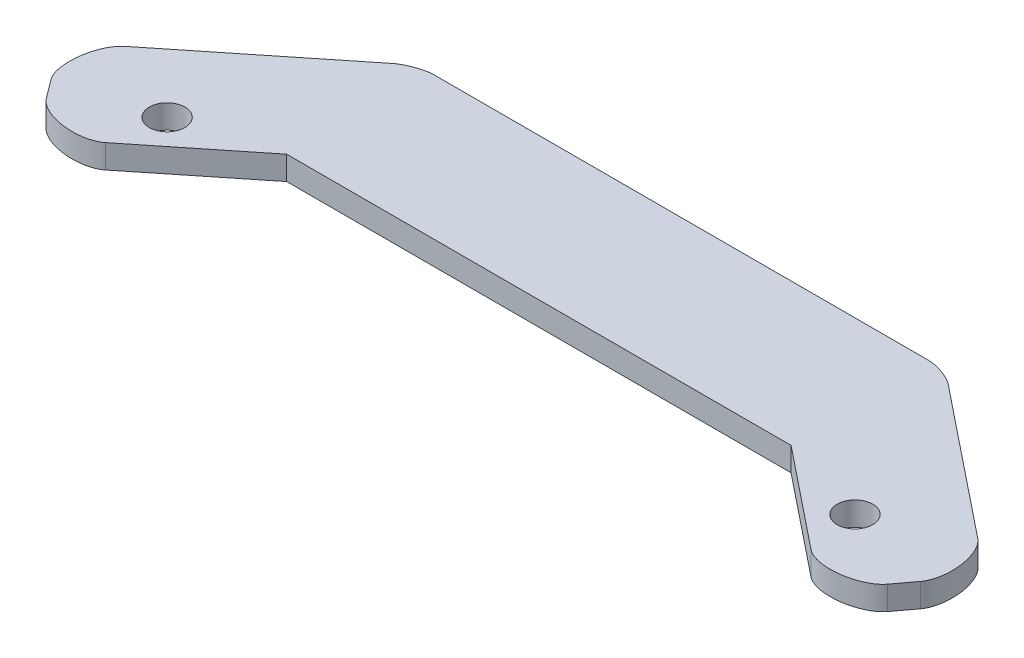
SolidWorks part; units mm, degrees
ref_plane "Front Plane" through (0, 0, 0) normal (0, 0, 1) x (1, 0, 0)
ref_plane "Top Plane" through (0, 0, 0) normal (0, 1, 0) x (1, 0, 0)
ref_plane "Right Plane" through (0, 0, 0) normal (1, 0, 0) x (0, 0, -1)
sketch "Sketch1" plane through (0, 0, 0) normal (0, 1, 0) x (1, 0, 0)
  line L0 (-13.635, -43.1454) -> (0.2556, -60.4948) construction
  line L5 (-13.635, -43.1454) -> (-22.9293, -50.5868) construction
  line L6 (-22.9293, -50.5868) -> (-9.0387, -67.9362) construction
  line L7 (-22.1678, 36.7724) -> (28.6322, 36.7724) construction
  line L8 (-22.1678, 36.7724) -> (-22.1678, -191.8276) construction
  line L9 (-22.1678, -191.8276) -> (28.6322, -191.8276) construction
  line L10 (28.6322, 36.7724) -> (28.6322, -191.8276) construction
  line L11 (0.2556, -60.4948) -> (-9.0387, -67.9362) construction
  line L12 (-13.635, -24.0954) -> (0.2556, -41.4448) construction
  line L13 (-13.635, -24.0954) -> (-22.9293, -31.5368) construction
  line L14 (-22.9293, -31.5368) -> (-9.0387, -48.8862) construction
  line L15 (-8.1122, -59.5683) -> (-27.1622, -59.5683) construction
  line L16 (-8.1122, -59.5683) -> (-8.1122, -40.5183) construction
  line L17 (0.2556, -41.4448) -> (-9.0387, -48.8862) construction
  line L18 (-8.1122, -40.5183) -> (-27.1622, -40.5183) construction
  line L19 (-8.1122, -40.5183) -> (-8.1122, -21.4683) construction
  line L20 (-13.635, -100.2954) -> (0.2556, -117.6448) construction
  line L21 (-13.635, -100.2954) -> (-22.9293, -107.7368) construction
  line L22 (-22.9293, -107.7368) -> (-9.0387, -125.0862) construction
  line L23 (0.2556, -117.6448) -> (-9.0387, -125.0862) construction
  line L24 (-13.635, -81.2454) -> (0.2556, -98.5948) construction
  line L25 (-13.635, -81.2454) -> (-22.9293, -88.6868) construction
  line L26 (-22.9293, -88.6868) -> (-9.0387, -106.0362) construction
  line L27 (-8.1122, -116.7183) -> (-27.1622, -116.7183) construction
  line L28 (-8.1122, -116.7183) -> (-8.1122, -97.6683) construction
  line L29 (0.2556, -98.5948) -> (-9.0387, -106.0362) construction
  line L30 (-8.1122, -97.6683) -> (-27.1622, -97.6683) construction
  line L31 (-8.1122, -97.6683) -> (-8.1122, -78.6183) construction
  line L32 (-13.635, -5.0454) -> (0.2556, -22.3948) construction
  line L33 (-13.635, -5.0454) -> (-22.9293, -12.4868) construction
  line L34 (-13.635, 14.0046) -> (0.2556, -3.3448) construction
  line L35 (-13.635, 14.0046) -> (-22.9293, 6.5632) construction
  line L36 (-22.9293, 6.5632) -> (-9.0387, -10.7862) construction
  line L37 (0.2556, -3.3448) -> (-9.0387, -10.7862) construction
  line L38 (-22.9293, -12.4868) -> (-9.0387, -29.8362) construction
  line L39 (0.2556, -22.3948) -> (-9.0387, -29.8362) construction
  line L40 (-13.635, 33.0546) -> (0.2556, 15.7052) construction
  line L41 (-13.635, 33.0546) -> (-22.9293, 25.6132) construction
  line L42 (-22.9293, 25.6132) -> (-9.0387, 8.2638) construction
  line L43 (0.2556, 15.7052) -> (-9.0387, 8.2638) construction
  line L44 (-8.1122, -21.4683) -> (-27.1622, -21.4683) construction
  line L45 (-8.1122, -21.4683) -> (-8.1122, -2.4183) construction
  line L46 (-13.635, -62.1954) -> (0.2556, -79.5448) construction
  line L47 (-13.635, -62.1954) -> (-22.9293, -69.6368) construction
  line L48 (-22.9293, -69.6368) -> (-9.0387, -86.9862) construction
  line L49 (0.2556, -79.5448) -> (-9.0387, -86.9862) construction
  line L50 (-8.1122, -78.6183) -> (-27.1622, -78.6183) construction
  line L51 (-8.1122, -78.6183) -> (-8.1122, -59.5683) construction
  line L52 (-8.1122, -2.4183) -> (-27.1622, -2.4183) construction
  line L53 (-8.1122, -2.4183) -> (-8.1122, 16.6317) construction
  line L54 (-8.1122, 16.6317) -> (-27.1622, 16.6317) construction
  line L55 (-8.1122, 16.6317) -> (-8.1122, 35.6817) construction
  line L56 (-22.9293, 25.6132) -> (-25.9059, 29.3309) construction
  line L57 (-25.9059, 29.3309) -> (-16.6116, 36.7724) construction
  line L58 (-16.6116, 36.7724) -> (-13.635, 33.0546) construction
  line L59 (-24.4176, 27.4721) -> (-15.1233, 34.9135) construction
  line L60 (-25.9059, 28.8165) -> (-25.9059, 40.1202) construction
  line L61 (-9.0387, 8.2638) -> (-6.0621, 4.5461) construction
  line L62 (-8.1122, 36.5878) -> (-8.1122, -24.5097) construction
  line L63 (-6.0621, 4.5461) -> (3.2322, 11.9875) construction
  line L64 (0.2556, 15.7052) -> (3.2322, 11.9875) construction
  line L65 (1.7439, 13.8464) -> (-7.5504, 6.405) construction
  line L66 (-19.7704, 30.6783) -> (-19.7704, 38.979) construction
  line L67 (-2.9032, 9.6112) -> (-2.9032, 17.9119) construction
  line L68 (3.2322, 11.4731) -> (3.2322, 48.1829) construction
  line L69 (4.7205, 13.8464) -> (14.0148, 6.405) construction
  line L70 (6.2088, 15.7052) -> (3.2322, 11.9875) construction
  line L71 (12.5265, 4.5461) -> (3.2322, 11.9875) construction
  line L72 (15.5031, 8.2638) -> (12.5265, 4.5461) construction
  line L73 (30.882, 27.4721) -> (21.5877, 34.9135) construction
  line L74 (23.0759, 36.7724) -> (20.0994, 33.0546) construction
  line L75 (32.3703, 29.3309) -> (23.0759, 36.7724) construction
  line L76 (29.3937, 25.6132) -> (32.3703, 29.3309) construction
  line L77 (14.5766, 16.6317) -> (14.5766, 35.6817) construction
  line L78 (14.5766, 16.6317) -> (33.6266, 16.6317) construction
  line L79 (14.5766, -2.4183) -> (14.5766, 16.6317) construction
  line L80 (14.5766, -2.4183) -> (33.6266, -2.4183) construction
  line L81 (14.5766, -78.6183) -> (14.5766, -59.5683) construction
  line L82 (14.5766, -78.6183) -> (33.6266, -78.6183) construction
  line L83 (6.2088, -79.5448) -> (15.5031, -86.9862) construction
  line L84 (29.3937, -69.6368) -> (15.5031, -86.9862) construction
  line L85 (20.0994, -62.1954) -> (29.3937, -69.6368) construction
  line L86 (20.0994, -62.1954) -> (6.2088, -79.5448) construction
  line L87 (14.5766, -21.4683) -> (14.5766, -2.4183) construction
  line L88 (14.5766, -21.4683) -> (33.6266, -21.4683) construction
  line L89 (6.2088, 15.7052) -> (15.5031, 8.2638) construction
  line L90 (29.3937, 25.6132) -> (15.5031, 8.2638) construction
  line L91 (20.0994, 33.0546) -> (29.3937, 25.6132) construction
  line L92 (20.0994, 33.0546) -> (6.2088, 15.7052) construction
  line L93 (6.2088, -22.3948) -> (15.5031, -29.8362) construction
  line L94 (29.3937, -12.4868) -> (15.5031, -29.8362) construction
  line L95 (6.2088, -3.3448) -> (15.5031, -10.7862) construction
  line L96 (29.3937, 6.5632) -> (15.5031, -10.7862) construction
  line L97 (20.0994, 14.0046) -> (29.3937, 6.5632) construction
  line L98 (20.0994, 14.0046) -> (6.2088, -3.3448) construction
  line L99 (20.0994, -5.0454) -> (29.3937, -12.4868) construction
  line L100 (20.0994, -5.0454) -> (6.2088, -22.3948) construction
  line L101 (14.5766, -97.6683) -> (14.5766, -78.6183) construction
  line L102 (14.5766, -97.6683) -> (33.6266, -97.6683) construction
  line L103 (6.2088, -98.5948) -> (15.5031, -106.0362) construction
  line L104 (14.5766, -116.7183) -> (14.5766, -97.6683) construction
  line L105 (14.5766, -116.7183) -> (33.6266, -116.7183) construction
  line L106 (29.3937, -88.6868) -> (15.5031, -106.0362) construction
  line L107 (20.0994, -81.2454) -> (29.3937, -88.6868) construction
  line L108 (20.0994, -81.2454) -> (6.2088, -98.5948) construction
  line L109 (6.2088, -117.6448) -> (15.5031, -125.0862) construction
  line L110 (29.3937, -107.7368) -> (15.5031, -125.0862) construction
  line L111 (20.0994, -100.2954) -> (29.3937, -107.7368) construction
  line L112 (20.0994, -100.2954) -> (6.2088, -117.6448) construction
  line L113 (14.5766, -40.5183) -> (14.5766, -21.4683) construction
  line L114 (14.5766, -40.5183) -> (33.6266, -40.5183) construction
  line L115 (6.2088, -41.4448) -> (15.5031, -48.8862) construction
  line L116 (14.5766, -59.5683) -> (14.5766, -40.5183) construction
  line L117 (14.5766, -59.5683) -> (33.6266, -59.5683) construction
  line L118 (29.3937, -31.5368) -> (15.5031, -48.8862) construction
  line L119 (20.0994, -24.0954) -> (29.3937, -31.5368) construction
  line L120 (20.0994, -24.0954) -> (6.2088, -41.4448) construction
  line L121 (6.2088, -60.4948) -> (15.5031, -67.9362) construction
  line L122 (29.3937, -50.5868) -> (15.5031, -67.9362) construction
  line L123 (20.0994, -43.1454) -> (29.3937, -50.5868) construction
  line L124 (20.0994, -43.1454) -> (6.2088, -60.4948) construction
  line L125 (23.0759, 36.7724) -> (-16.6116, 36.7724) construction
  circle A2 centre (-8.1122, -59.5683) radius 5.9531 construction
  circle A3 centre (-8.1122, -59.5683) radius 19.05 construction
  circle A4 centre (-8.1122, -40.5183) radius 5.9531 construction
  circle A5 centre (-8.1122, -40.5183) radius 19.05 construction
  circle A6 centre (-8.1122, -116.7183) radius 5.9531 construction
  circle A7 centre (-8.1122, -116.7183) radius 19.05 construction
  circle A8 centre (-8.1122, -97.6683) radius 5.9531 construction
  circle A9 centre (-8.1122, -97.6683) radius 19.05 construction
  circle A10 centre (-8.1122, -2.4183) radius 5.9531 construction
  circle A11 centre (-8.1122, -2.4183) radius 19.05 construction
  circle A12 centre (-8.1122, 16.6317) radius 5.9531 construction
  circle A13 centre (-8.1122, 16.6317) radius 19.05 construction
  circle A14 centre (-8.1122, -21.4683) radius 5.9531 construction
  circle A15 centre (-8.1122, -21.4683) radius 19.05 construction
  circle A16 centre (-8.1122, -78.6183) radius 5.9531 construction
  circle A17 centre (-8.1122, -78.6183) radius 19.05 construction
  circle A18 centre (-19.7704, 31.1928) radius 1.1906
  circle A19 centre (-2.9032, 10.1257) radius 1.1906
  circle A20 centre (14.5766, -78.6183) radius 19.05 construction
  circle A21 centre (14.5766, -78.6183) radius 5.9531 construction
  circle A22 centre (14.5766, -21.4683) radius 19.05 construction
  circle A23 centre (14.5766, -21.4683) radius 5.9531 construction
  circle A24 centre (14.5766, 16.6317) radius 19.05 construction
  circle A25 centre (14.5766, 16.6317) radius 5.9531 construction
  circle A26 centre (14.5766, -2.4183) radius 19.05 construction
  circle A27 centre (14.5766, -2.4183) radius 5.9531 construction
  circle A28 centre (14.5766, -97.6683) radius 19.05 construction
  circle A29 centre (14.5766, -97.6683) radius 5.9531 construction
  circle A30 centre (14.5766, -116.7183) radius 19.05 construction
  circle A31 centre (14.5766, -116.7183) radius 5.9531 construction
  circle A32 centre (14.5766, -40.5183) radius 19.05 construction
  circle A33 centre (14.5766, -40.5183) radius 5.9531 construction
  circle A34 centre (14.5766, -59.5683) radius 19.05 construction
  circle A35 centre (14.5766, -59.5683) radius 5.9531 construction
  circle A36 centre (9.3676, 10.1257) radius 1.1906
  circle A37 centre (26.2348, 31.1928) radius 1.1906
  point P81 (-15.1233, 34.9135)
  point P97 (3.2322, 36.7724)
  dimension "D3" = 2.3813
  dimension "D23" = 38.1
  dimension "D1" = 4.7625
  dimension "D4" = 50.8
  dimension "D5" = 228.6
  dimension "D21" = 22.225
  dimension "D22" = 11.9062
sketch "Sketch2" plane through (0, 0, 0) normal (0, 1, 0) x (1, 0, 0)
  line L0 (-16.6116, 36.7724) -> (-13.635, 33.0546)
  line L1 (-13.635, 33.0546) -> (-22.9293, 25.6132)
  line L2 (-22.9293, 25.6132) -> (-13.635, 14.0046)
  line L3 (-18.2822, 10.2839) -> (-19.7704, 12.1428)
  line L4 (-13.635, 14.0046) -> (-22.9293, 6.5632) construction
  line L5 (-19.7704, -199969.3217) -> (-19.7704, 200038.979) construction
  line L6 (3.2322, 37.6418) -> (3.2322, 34.7632) construction
  line L7 (-9.0387, -10.7862) -> (0.2556, -22.3948)
  line L8 (3.2322, -199988.5269) -> (3.2322, 200048.1829) construction
  line L9 (-13.635, 14.0046) -> (-22.9293, 6.5632)
  line L10 (-22.9293, 6.5632) -> (-13.635, -5.0454)
  line L11 (-13.635, -5.0454) -> (-22.9293, -12.4868)
  line L12 (-22.9293, -12.4868) -> (-13.635, -24.0954)
  line L13 (-13.635, -24.0954) -> (-22.9293, -31.5368)
  line L14 (-22.9293, -31.5368) -> (-13.635, -43.1454)
  line L15 (-13.635, -43.1454) -> (-22.9293, -50.5868)
  line L16 (-22.9293, -50.5868) -> (-13.635, -62.1954)
  line L17 (-13.635, -62.1954) -> (-22.9293, -69.6368)
  line L18 (-22.9293, -69.6368) -> (-13.635, -81.2454)
  line L19 (-13.635, -81.2454) -> (-22.9293, -88.6868)
  line L20 (-22.9293, -88.6868) -> (-13.635, -100.2954)
  line L21 (-13.635, -100.2954) -> (-22.9293, -107.7368)
  line L22 (-22.9293, -107.7368) -> (-13.635, -119.3454)
  line L23 (0.2556, 15.7052) -> (-9.0387, 8.2638)
  line L24 (-9.0387, 8.2638) -> (0.2556, -3.3448)
  line L25 (0.2556, -3.3448) -> (-9.0387, -10.7862)
  line L26 (-9.0387, -29.8362) -> (0.2556, -41.4448)
  line L27 (0.2556, -22.3948) -> (-9.0387, -29.8362)
  line L28 (-9.0387, -48.8862) -> (0.2556, -60.4948)
  line L29 (0.2556, -41.4448) -> (-9.0387, -48.8862)
  line L30 (-9.0387, -67.9362) -> (0.2556, -79.5448)
  line L31 (0.2556, -60.4948) -> (-9.0387, -67.9362)
  line L32 (-9.0387, -86.9862) -> (0.2556, -98.5948)
  line L33 (0.2556, -79.5448) -> (-9.0387, -86.9862)
  line L34 (-9.0387, -106.0362) -> (0.2556, -117.6448)
  line L35 (0.2556, -98.5948) -> (-9.0387, -106.0362)
  line L37 (0.2556, -117.6448) -> (-9.0387, -125.0862)
  line L38 (6.2088, -117.6448) -> (15.5031, -125.0862)
  line L39 (-9.0387, -125.0862) -> (0.2556, -136.6948)
  line L41 (-22.9293, 25.6132) -> (-27.6918, 25.6132) construction
  line L42 (-16.6116, 36.7724) -> (-27.6918, 36.7724)
  line L43 (-27.6918, 36.7724) -> (-27.6918, -124.1079)
  line L44 (-13.635, -119.3454) -> (-13.635, -124.1079)
  line L45 (-13.635, -124.1079) -> (-27.6918, -124.1079)
  line L47 (6.2088, -98.5948) -> (15.5031, -106.0362)
  line L48 (15.5031, -106.0362) -> (6.2088, -117.6448)
  line L49 (6.2088, -79.5448) -> (15.5031, -86.9862)
  line L50 (15.5031, -86.9862) -> (6.2088, -98.5948)
  line L51 (6.2088, -60.4948) -> (15.5031, -67.9362)
  line L52 (15.5031, -67.9362) -> (6.2088, -79.5448)
  line L53 (6.2088, -41.4448) -> (15.5031, -48.8862)
  line L54 (15.5031, -48.8862) -> (6.2088, -60.4948)
  line L55 (6.2088, -22.3948) -> (15.5031, -29.8362)
  line L56 (15.5031, -29.8362) -> (6.2088, -41.4448)
  line L57 (6.2088, -3.3448) -> (15.5031, -10.7862)
  line L58 (15.5031, 8.2638) -> (6.2088, -3.3448)
  line L59 (6.2088, 15.7052) -> (15.5031, 8.2638)
  line L60 (15.5031, -10.7862) -> (6.2088, -22.3948)
  line L61 (0.2556, 15.7052) -> (6.2088, 15.7052)
  line L62 (29.3937, 25.6132) -> (34.1562, 25.6132) construction
  line L63 (20.0994, -124.1079) -> (34.1562, -124.1079)
  line L64 (20.0994, -119.3454) -> (20.0994, -124.1079)
  line L65 (34.1562, 36.7724) -> (34.1562, -124.1079)
  line L66 (23.0759, 36.7724) -> (34.1562, 36.7724)
  line L67 (29.3937, -107.7368) -> (20.0994, -119.3454)
  line L68 (20.0994, -100.2954) -> (29.3937, -107.7368)
  line L69 (29.3937, -88.6868) -> (20.0994, -100.2954)
  line L70 (20.0994, -81.2454) -> (29.3937, -88.6868)
  line L71 (29.3937, -69.6368) -> (20.0994, -81.2454)
  line L72 (20.0994, -62.1954) -> (29.3937, -69.6368)
  line L73 (29.3937, -50.5868) -> (20.0994, -62.1954)
  line L74 (20.0994, -43.1454) -> (29.3937, -50.5868)
  line L75 (29.3937, -31.5368) -> (20.0994, -43.1454)
  line L76 (20.0994, -24.0954) -> (29.3937, -31.5368)
  line L77 (29.3937, -12.4868) -> (20.0994, -24.0954)
  line L78 (20.0994, -5.0454) -> (29.3937, -12.4868)
  line L79 (29.3937, 6.5632) -> (20.0994, -5.0454)
  line L80 (20.0994, 14.0046) -> (29.3937, 6.5632)
  line L81 (24.7465, 10.2839) -> (26.2348, 12.1428)
  line L82 (29.3937, 25.6132) -> (20.0994, 14.0046)
  line L83 (20.0994, 33.0546) -> (29.3937, 25.6132)
  line L84 (23.0759, 36.7724) -> (20.0994, 33.0546)
  line L85 (-27.6918, 31.9683) -> (-21.6916, 36.7724)
  line L86 (28.1559, 36.7724) -> (34.1562, 31.9683)
  line L87 (-22.9293, -107.7368) -> (-27.6918, -101.7884)
  line L88 (29.3937, -107.7368) -> (34.1562, -101.7884)
  line L89 (-9.0387, -125.0862) -> (-6.0621, -128.8039)
  line L90 (15.5031, -125.0862) -> (12.5265, -128.8039)
  line L91 (-6.0621, -128.8039) -> (12.5265, -128.8039)
  line L92 (-25.9059, 29.3309) -> (-16.6116, 36.7724) construction
  line L93 (32.3703, 29.3309) -> (23.0759, 36.7724) construction
  circle A0 centre (-19.7704, 31.1928) radius 1.1906
  circle A1 centre (-19.7704, 31.1928) radius 1.1906 construction
  circle A2 centre (-19.7704, 12.1428) radius 1.1906
  circle A3 centre (-19.7704, -6.9072) radius 1.1906
  circle A4 centre (-19.7704, -25.9572) radius 1.1906
  circle A5 centre (-19.7704, -45.0072) radius 1.1906
  circle A6 centre (-19.7704, -64.0572) radius 1.1906
  circle A7 centre (-19.7704, -83.1072) radius 1.1906
  circle A8 centre (-19.7704, -102.1572) radius 1.1906
  circle A9 centre (-2.9032, 10.1257) radius 1.1906
  circle A10 centre (-2.9032, 10.1257) radius 1.1906 construction
  circle A11 centre (-2.9032, -8.9243) radius 1.1906
  circle A12 centre (-2.9032, -27.9743) radius 1.1906
  circle A13 centre (-2.9032, -47.0243) radius 1.1906
  circle A14 centre (-2.9032, -66.0743) radius 1.1906
  circle A15 centre (-2.9032, -85.1243) radius 1.1906
  circle A16 centre (-2.9032, -104.1743) radius 1.1906
  circle A17 centre (-2.9032, -123.2243) radius 1.1906
  circle A18 centre (9.3676, -123.2243) radius 1.1906
  circle A19 centre (9.3676, -104.1743) radius 1.1906
  circle A20 centre (9.3676, -85.1243) radius 1.1906
  circle A21 centre (9.3676, -66.0743) radius 1.1906
  circle A22 centre (9.3676, -47.0243) radius 1.1906
  circle A23 centre (9.3676, -27.9743) radius 1.1906
  circle A24 centre (9.3676, -8.9243) radius 1.1906
  circle A25 centre (9.3676, 10.1257) radius 1.1906
  circle A26 centre (26.2348, -102.1572) radius 1.1906
  circle A27 centre (26.2348, -83.1072) radius 1.1906
  circle A28 centre (26.2348, -64.0572) radius 1.1906
  circle A29 centre (26.2348, -45.0072) radius 1.1906
  circle A30 centre (26.2348, -25.9572) radius 1.1906
  circle A31 centre (26.2348, -6.9072) radius 1.1906
  circle A32 centre (26.2348, 12.1428) radius 1.1906
  circle A33 centre (26.2348, 31.1928) radius 1.1906
  dimension "D1" = 19.05
  dimension "D3" = 8
  dimension "D2" = 8
  dimension "D4" = 3.175
  dimension "D5" = 3.175
sketch "Sketch3" plane through (0, 0, 0) normal (0, 1, 0) x (1, 0, 0)
  line L0 (-22.9293, 25.6132) -> (-13.635, 33.0546)
  line L1 (-13.635, 33.0546) -> (20.0994, 33.0546)
  line L2 (20.0994, 33.0546) -> (29.3937, 25.6132)
  line L3 (29.3937, 25.6132) -> (34.1562, 31.9683)
  line L4 (34.1562, 31.9683) -> (24.8619, 39.4097)
  line L5 (-22.9293, 25.6132) -> (-27.6918, 31.9683)
  line L6 (-27.6918, 31.9683) -> (-18.3975, 39.4097)
  line L7 (-14.4383, 42.5796) -> (20.9027, 42.5796)
  line L8 (-13.635, 33.0546) -> (-18.3975, 39.4097) construction
  line L9 (24.8619, 39.4097) -> (20.0994, 33.0546) construction
  line L10 (3.2322, 33.0546) -> (3.2322, 42.5796) construction
  line L11 (-18.3975, 39.4097) -> (-14.4383, 42.5796)
  line L12 (20.9027, 42.5796) -> (24.8619, 39.4097)
  circle A0 centre (-19.7704, 31.1928) radius 1.1906
  circle A1 centre (26.2348, 31.1928) radius 1.1906
  circle A2 centre (-19.7704, 31.1928) radius 1.1906 construction
  point P26 (3.2322, 42.5796)
  dimension "D1" = 9.525
extrude "Boss-Extrude1" add sketch "Sketch3" along normal blind 1.5875
fillet "Fillet1" radius 3.175 6 edges at (-22.9293, 0.7937, -25.6132) (29.3937, 0.7937, -25.6132) (-27.6918, 0.7937, -31.9683) (34.1562, 0.7937, -31.9683) (20.9027, 0.7937, -42.5796) (-14.4383, 0.7937, -42.5796) conic radius 4.92
